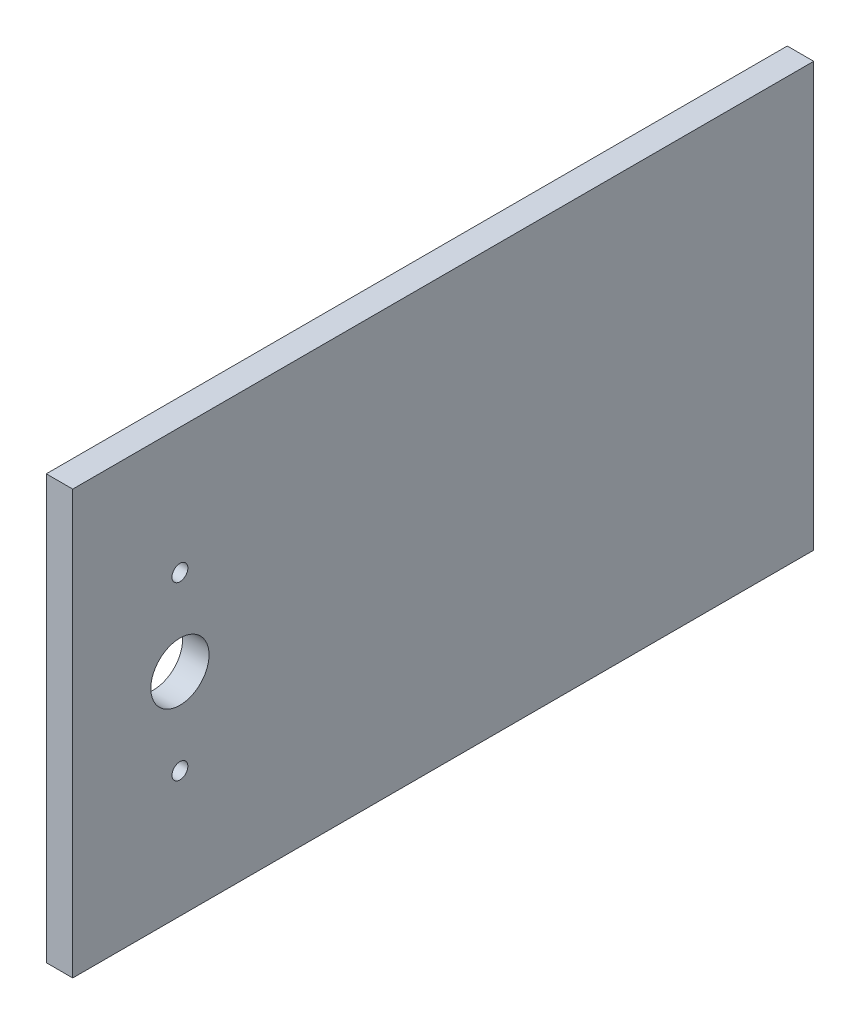
SolidWorks part; units mm, degrees
ref_plane "Front Plane" through (0, 0, 0) normal (1, 0, 0) x (0, 1, 0)
ref_plane "Top Plane" through (0, 0, 0) normal (0, 0, 1) x (0, 1, 0)
ref_plane "Right Plane" through (0, 0, 0) normal (0, 1, 0) x (-1, 0, 0)
sketch "Sketch1" plane through (0, 0, 0) normal (1, 0, 0) x (0, 1, 0)
  line L0 (0, 70) -> (0, -70) construction
  line L1 (-40, -70) -> (40, -70)
  line L2 (-40, -70) -> (-40, 70)
  line L3 (-40, 70) -> (40, 70)
  line L4 (40, -70) -> (40, 70)
  line L5 (-40, -70) -> (40, 70) construction
  line L6 (-40, 70) -> (40, -70) construction
  line L7 (-40, 49.75) -> (40, 49.75) construction
  circle A5 centre (0, 49.75) radius 5.5
  circle A6 centre (-16.22, 49.75) radius 1.5
  circle A7 centre (16.22, 49.75) radius 1.5
  point P0 (0, 0)
  dimension "D5" = 16.22
  dimension "D8" = 11
  dimension "D4" = 3
  dimension "D1" = 80
  dimension "D2" = 140
  dimension "D3" = 119.75
extrude "Boss-Extrude1" add sketch "Sketch1" along normal blind 5
